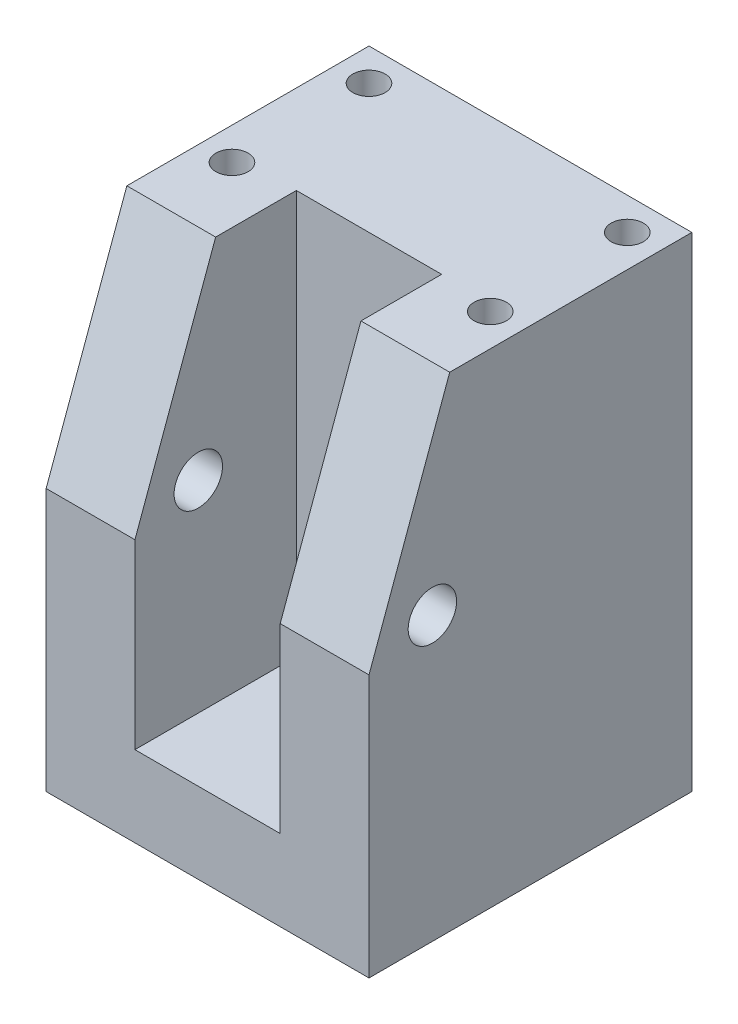
SolidWorks part; units mm, degrees
material "6061-T6 (SS)"
ref_plane "Front Plane" through (0, 0, 0) normal (0, 0, 1) x (1, 0, 0)
ref_plane "Top Plane" through (0, 0, 0) normal (0, 1, 0) x (1, 0, 0)
ref_plane "Right Plane" through (0, 0, 0) normal (1, 0, 0) x (0, 0, -1)
sketch "Sketch1" plane through (0, 0, 0) normal (0, 1, 0) x (1, 0, 0)
  line L0 (9, -20) -> (-9, -20)
  line L1 (-20, 20) -> (20, 20)
  line L2 (-20, 20) -> (-20, -20)
  line L3 (-20, -20) -> (20, -20)
  line L4 (20, 20) -> (20, -20)
  line L5 (-20, 20) -> (20, -20) construction
  line L6 (-20, -20) -> (20, 20) construction
  line L7 (9, -20) -> (9, 0)
  line L8 (-9, -20) -> (-9, 0)
  line L9 (9, 0) -> (-9, 0)
  point P0 (0, 0)
  point P6 (0, -20)
  point P9 (0, -20)
  dimension "D1" = 18
  dimension "D2" = 40
  dimension "D3" = 40
  dimension "D4" = 20
extrude "Boss-Extrude1" add sketch "Sketch1" against normal blind 60 contours L7 L9 L8 L0 | L9 L7 L3 L4 L1 L2 L8 region at (0, 0, -2.9032) region at (0, 0, 10)
extrude "Cut-Extrude1" cut sketch "Sketch1<3>" against normal blind 50 contours L7 L9 L8 L0 region at (0, 0, 10)
sketch "Sketch1<3>" plane through (0, 0, 0) normal (0, 1, 0) x (1, 0, 0) same geometry as "Sketch1"
sketch "Sketch3" plane through (0, 0, 0) normal (0, 0, 1) x (1, 0, 0)
  line L0 (9, 0) -> (-9, 0) construction
  line L1 (9, -50) -> (-9, -50) construction
  circle A0 centre (0, -4) radius 2
  circle A1 centre (0, -42) radius 2
  dimension "D1" = 4
  dimension "D2" = 4
  dimension "D3" = 8
extrude "Cut-Extrude2" [suppressed] cut sketch "Sketch3" against normal blind 34
sketch "Sketch4" plane through (0, 0, 0) normal (0, 1, 0) x (1, 0, 0)
  line L1 (-16, -0.977) -> (16, -0.977) construction
  line L2 (-16, -0.977) -> (-16, 16) construction
  line L3 (-16, 16) -> (16, 16) construction
  line L4 (16, -0.977) -> (16, 16) construction
  circle A0 centre (-16, 16) radius 2
  circle A1 centre (16, 16) radius 2
  circle A2 centre (16, -0.977) radius 2
  circle A3 centre (-16, -0.977) radius 2
  point P0 (0, 0)
  dimension "D2" = 4
  dimension "D1" = 32
  dimension "D3" = 16
  dimension "D4" = 16
extrude "Cut-Extrude3" cut sketch "Sketch4" against normal blind 70 and the other way blind 28
sketch "Sketch5" plane through (9, 0, 0) normal (-1, 0, 0) x (0, 0, 1)
  line L0 (20, -50) -> (0, -50) construction
  circle A0 centre (12.1487, -25) radius 3
  dimension "D1" = 6
  dimension "D2" = 25
extrude "Cut-Extrude4" cut sketch "Sketch5" against normal blind 57 and the other way blind 57
chamfer "Chamfer1" distance 10 angle 70 2 edges at (14.5, 0, 20) (-14.5, 0, 20) first distance on face at (-16, 0, 2.977)
